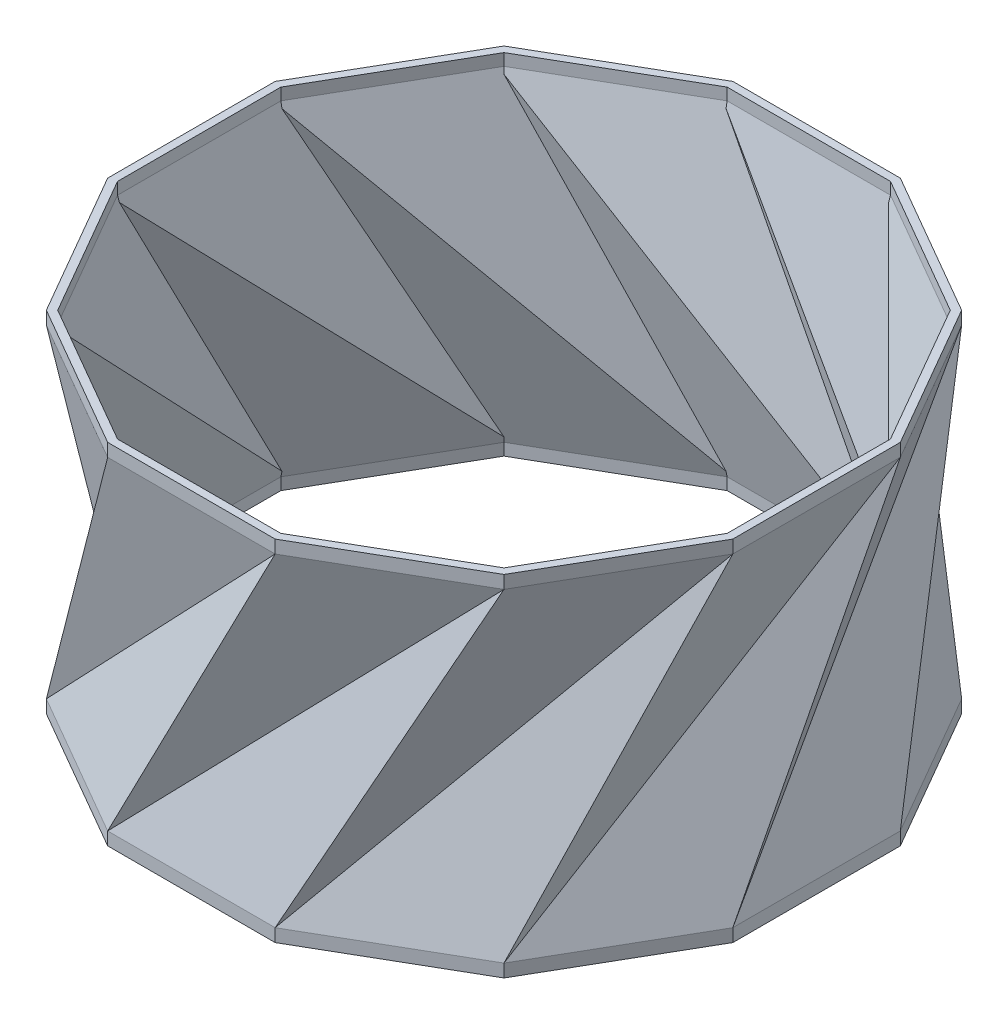
SolidWorks part; units mm, degrees
ref_plane "정면" through (0, 0, 0) normal (0, 0, 1) x (1, 0, 0)
ref_plane "윗면" through (0, 0, 0) normal (0, 1, 0) x (1, 0, 0)
ref_plane "우측면" through (0, 0, 0) normal (1, 0, 0) x (0, 0, -1)
sketch "스케치1" plane through (0, 0, 0) normal (0, 1, 0) x (1, 0, 0)
  line L0 (-55, 0) -> (55, 0) construction
  line L1 (17.6777, -17.6777) -> (24.1481, -6.4705)
  line L2 (24.1481, -6.4705) -> (24.1481, 6.4705)
  line L3 (24.1481, 6.4705) -> (17.6777, 17.6777)
  line L4 (17.6777, 17.6777) -> (6.4705, 24.1481)
  line L5 (6.4705, 24.1481) -> (-6.4705, 24.1481)
  line L6 (-6.4705, 24.1481) -> (-17.6777, 17.6777)
  line L7 (-17.6777, 17.6777) -> (-24.1481, 6.4705)
  line L8 (-24.1481, 6.4705) -> (-24.1481, -6.4705)
  line L9 (-24.1481, -6.4705) -> (-17.6777, -17.6777)
  line L10 (-17.6777, -17.6777) -> (-6.4705, -24.1481)
  line L11 (-6.4705, -24.1481) -> (6.4705, -24.1481)
  line L12 (6.4705, -24.1481) -> (17.6777, -17.6777)
  circle A0 centre (0, 0) radius 25 construction
  dimension "D1" = 50
extrude "보스-돌출1" add sketch "스케치1" along normal blind 25
ref_plane "평면1" through (0, 5.8576, 22.6321) normal (0, 0.2506, 0.9681) x (1, 0, 0)
sketch "스케치2" plane through (0, 5.8576, 22.6321) normal (0, 0.2506, 0.9681) x (1, 0, 0)
  line L0 (-6.4705, -6.0506) -> (17.6777, 19.7731)
  line L1 (17.6777, 19.7731) -> (6.4705, -6.0506)
sketch "스케치3" plane through (0, 0, 24.1481) normal (0, 0, 1) x (1, 0, 0)
  line L0 (-6.4705, 0) -> (6.4705, 25)
ref_plane "평면2" through (-6.4705, 0, 24.1481) normal (0.683, 0.7071, -0.183) x (0.7304, -0.6612, 0.1711)
sketch "스케치4" plane through (-6.4705, 0, 24.1481) normal (0.683, 0.7071, -0.183) x (0.7304, -0.6612, 0.1711)
  line L0 (0, 0) -> (-7.0785, -6.2641) construction
  line L1 (0, 0) -> (9.4522, 0) construction
  line L2 (0, 0) -> (-7.0785, -6.2641)
  line L3 (0, 0) -> (9.4522, 0)
  line L4 (-7.0785, -6.2641) -> (9.4522, 0)
extrude "컷-돌출1" cut sketch "스케치4" along normal up to vertex (35.3553 mm away) up to point (17.6777, 25, 17.6777)
pattern_circular "원형 패턴1" count 12 over 360 about axis through (0, 25, 0) along (0, 1, 0) of "컷-돌출1"
sketch "스케치5" plane through (0, 25, 0) normal (0, 1, 0) x (1, 0, 0)
  line L12 (6.4705, -24.1481) -> (17.6777, -17.6777)
  line L13 (17.6777, -17.6777) -> (24.1481, -6.4705)
  line L14 (24.1481, -6.4705) -> (24.1481, 6.4705)
  line L15 (24.1481, 6.4705) -> (17.6777, 17.6777)
  line L16 (17.6777, 17.6777) -> (6.4705, 24.1481)
  line L17 (6.4705, 24.1481) -> (-6.4705, 24.1481)
  line L18 (-6.4705, 24.1481) -> (-17.6777, 17.6777)
  line L19 (-17.6777, 17.6777) -> (-24.1481, 6.4705)
  line L20 (-24.1481, 6.4705) -> (-24.1481, -6.4705)
  line L21 (-24.1481, -6.4705) -> (-17.6777, -17.6777)
  line L22 (-17.6777, -17.6777) -> (-6.4705, -24.1481)
  line L23 (-6.4705, -24.1481) -> (6.4705, -24.1481)
  line L24 (6.4705, -24.1481) -> (17.6777, -17.6777)
  line L25 (17.6777, -17.6777) -> (24.1481, -6.4705)
  line L26 (24.1481, -6.4705) -> (24.1481, 6.4705)
  line L27 (24.1481, 6.4705) -> (17.6777, 17.6777)
  line L28 (17.6777, 17.6777) -> (6.4705, 24.1481)
  line L29 (6.4705, 24.1481) -> (-6.4705, 24.1481)
  line L30 (-6.4705, 24.1481) -> (-17.6777, 17.6777)
  line L31 (-17.6777, 17.6777) -> (-24.1481, 6.4705)
  line L32 (-24.1481, 6.4705) -> (-24.1481, -6.4705)
  line L33 (-24.1481, -6.4705) -> (-17.6777, -17.6777)
  line L34 (-17.6777, -17.6777) -> (-6.4705, -24.1481)
  line L35 (-6.4705, -24.1481) -> (6.4705, -24.1481)
  dimension "D1" = 0
extrude "보스-돌출2" add sketch "스케치5" along normal blind 1
sketch "스케치6" plane through (0, 0, 0) normal (0, -1, 0) x (1, 0, 0)
  line L12 (17.6777, 17.6777) -> (6.4705, 24.1481)
  line L13 (6.4705, 24.1481) -> (-6.4705, 24.1481)
  line L14 (-6.4705, 24.1481) -> (-17.6777, 17.6777)
  line L15 (-17.6777, 17.6777) -> (-24.1481, 6.4705)
  line L16 (-24.1481, 6.4705) -> (-24.1481, -6.4705)
  line L17 (-24.1481, -6.4705) -> (-17.6777, -17.6777)
  line L18 (-17.6777, -17.6777) -> (-6.4705, -24.1481)
  line L19 (-6.4705, -24.1481) -> (6.4705, -24.1481)
  line L20 (6.4705, -24.1481) -> (17.6777, -17.6777)
  line L21 (17.6777, -17.6777) -> (24.1481, -6.4705)
  line L22 (24.1481, -6.4705) -> (24.1481, 6.4705)
  line L23 (24.1481, 6.4705) -> (17.6777, 17.6777)
  line L24 (17.6777, 17.6777) -> (6.4705, 24.1481)
  line L25 (6.4705, 24.1481) -> (-6.4705, 24.1481)
  line L26 (-6.4705, 24.1481) -> (-17.6777, 17.6777)
  line L27 (-17.6777, 17.6777) -> (-24.1481, 6.4705)
  line L28 (-24.1481, 6.4705) -> (-24.1481, -6.4705)
  line L29 (-24.1481, -6.4705) -> (-17.6777, -17.6777)
  line L30 (-17.6777, -17.6777) -> (-6.4705, -24.1481)
  line L31 (-6.4705, -24.1481) -> (6.4705, -24.1481)
  line L32 (6.4705, -24.1481) -> (17.6777, -17.6777)
  line L33 (17.6777, -17.6777) -> (24.1481, -6.4705)
  line L34 (24.1481, -6.4705) -> (24.1481, 6.4705)
  line L35 (24.1481, 6.4705) -> (17.6777, 17.6777)
  dimension "D1" = 0
extrude "보스-돌출3" add sketch "스케치6" along normal blind 1
shell "쉘1" thickness 0.6 removed face at (0, 26, 0) removed face at (0, -1, 0)
